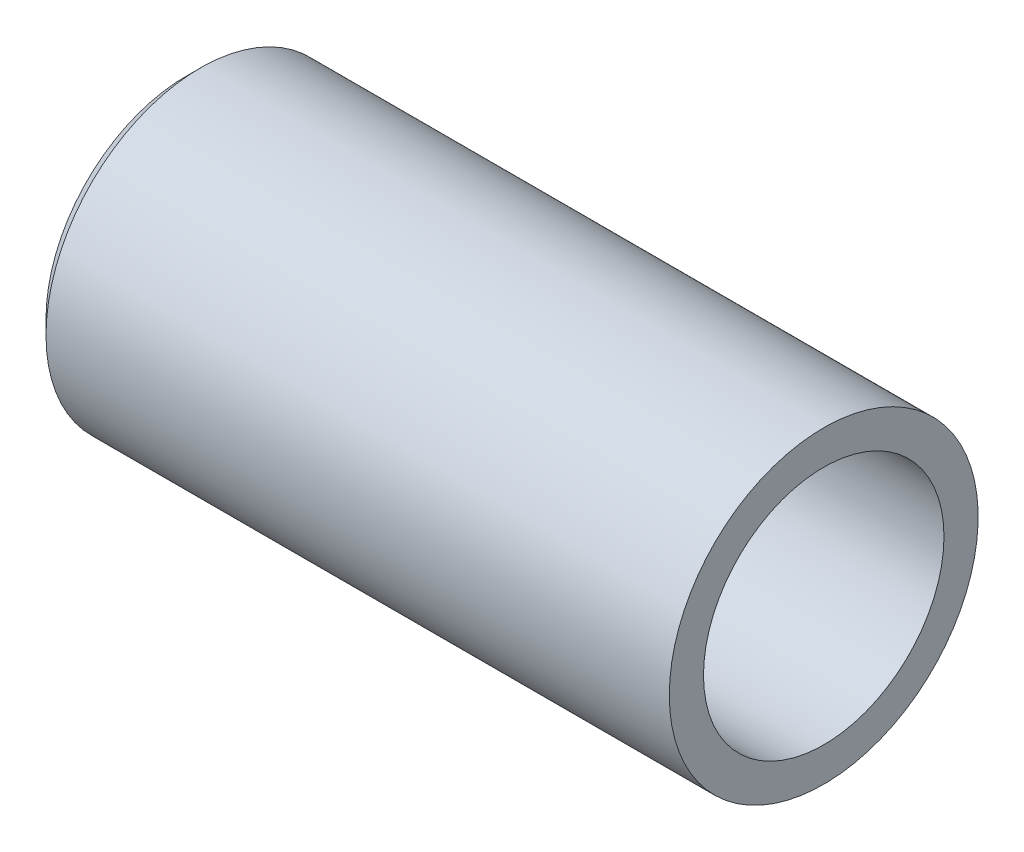
SolidWorks part; units mm, degrees
material "Nylon 6/10"
ref_plane "Front Plane" through (0, 0, 0) normal (0, 0, 1) x (1, 0, 0)
ref_plane "Top Plane" through (0, 0, 0) normal (0, 1, 0) x (1, 0, 0)
ref_plane "Right Plane" through (0, 0, 0) normal (1, 0, 0) x (0, 0, -1)
sketch "Sketch1" plane through (0, 0, 0) normal (0, 0, 1) x (1, 0, 0)
  line L0 (0, 0) -> (22.1407, 0) construction
  line L1 (3.0033, 5.4227) -> (24.892, 5.4227)
  line L3 (2.5063, 4.2228) -> (24.892, 4.2228)
  line L4 (25.4, 5.4227) -> (25.4, 4.2228) construction
  line L5 (24.892, 5.4227) -> (24.892, 4.2228)
  line L6 (50.5354, 3.9688) -> (-48.4378, 3.9688) construction
  line L7 (2.5063, -4.1672) -> (2.5063, 4.1672) construction
  line L8 (2.5063, 4.2228) -> (2.5063, 4.9257)
  line L9 (2.5063, 4.9257) -> (3.0033, 5.4227)
  line L10 (25.4, 36.4443) -> (25.4, 18.146) construction
  dimension "D4" = 45
  dimension "D2" = 1.2
  dimension "D1" = 0.254
  dimension "D3" = 0.508
revolve "Revolve1" add sketch "Sketch1" angle 360 about L0
equation "\"D2@Sketch1\"=1.2mm"
